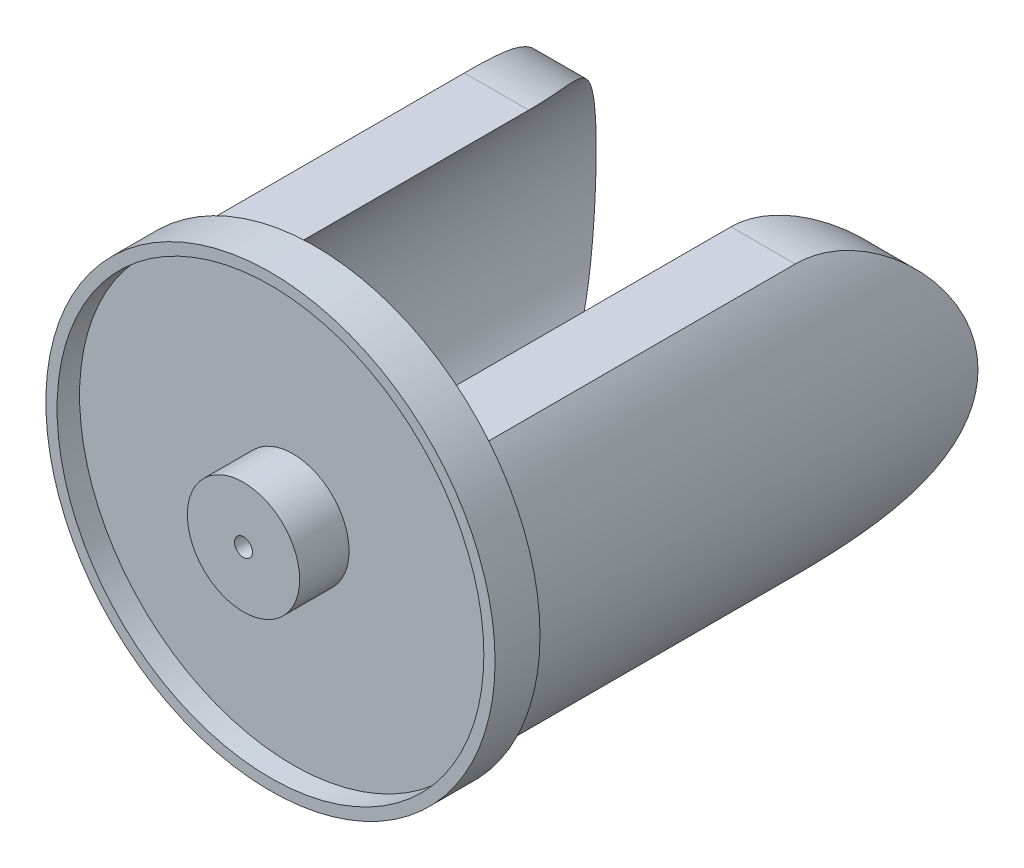
SolidWorks part; units mm, degrees
ref_plane "Plan de face" through (0, 0, 0) normal (0, 0, 1) x (1, 0, 0)
ref_plane "Plan de dessus" through (0, 0, 0) normal (0, 1, 0) x (1, 0, 0)
ref_plane "Plan de droite" through (0, 0, 0) normal (1, 0, 0) x (0, 0, -1)
sketch "Esquisse1" plane through (0, 0, 0) normal (0, 0, 1) x (1, 0, 0)
  circle A0 centre (0, 0) radius 50
  dimension "D1" = 100
extrude "Boss.-Extru.1" add sketch "Esquisse1" along normal blind 10
sketch "Esquisse2" plane through (0, 0, 10) normal (0, 0, 1) x (1, 0, 0)
  circle A0 centre (0, 0) radius 47.5
  dimension "D1" = 95
extrude "Enlèv. mat.-Extru.1" cut sketch "Esquisse2" against normal blind 5
sketch "Esquisse3" plane through (0, 0, 0) normal (0, 0, -1) x (-1, 0, 0)
  circle A0 centre (0, 0) radius 2
  dimension "D1" = 4
extrude "Enlèv. mat.-Extru.2" cut sketch "Esquisse3" against normal blind 5
sketch "Esquisse4" plane through (0, 0, 0) normal (0, 0, -1) x (-1, 0, 0)
  line L0 (-50, 0) -> (-35, 0) construction
  line L1 (-22.5, 30) -> (-22.5, -30)
  line L2 (-22.5, 30) -> (-36.8273, 30)
  line L3 (-22.5, -30) -> (-36.8273, -30)
  line L4 (0, 50) -> (0, -50) construction
  line L5 (22.5, -30) -> (36.8273, -30)
  line L6 (22.5, 30) -> (36.8273, 30)
  circle A1 centre (0, 0) radius 50 construction
  circle A2 centre (0, 0) radius 37.5
  circle A3 centre (0, 0) radius 47.5
  dimension "D1" = 10
  dimension "D2" = 60
  dimension "D3" = 2.5
extrude "Boss.-Extru.2" add sketch "Esquisse4" along normal blind 100 contours L2 A3 L3 A2 | L5 A3 L6 A2 region at (38.1648, 0, 0) region at (-38.1648, 0, 0)
fillet "Congé1" radius 30 4 edges at (29.6636, -30, -100) (29.6636, 30, -100) (-29.6636, -30, -100) (-29.6636, 30, -100)
sketch "Esquisse5" plane through (0, 0, 5) normal (0, 0, 1) x (1, 0, 0)
  circle A0 centre (0, 0) radius 12.5
  dimension "D1" = 25
extrude "Boss.-Extru.3" add sketch "Esquisse5" along normal blind 11
sketch "Esquisse6" plane through (0, 0, 16) normal (0, 0, 1) x (1, 0, 0)
  circle A0 centre (0, 0) radius 2
  dimension "D1" = 4
extrude "Enlèv. mat.-Extru.3" cut sketch "Esquisse6" against normal blind 11
